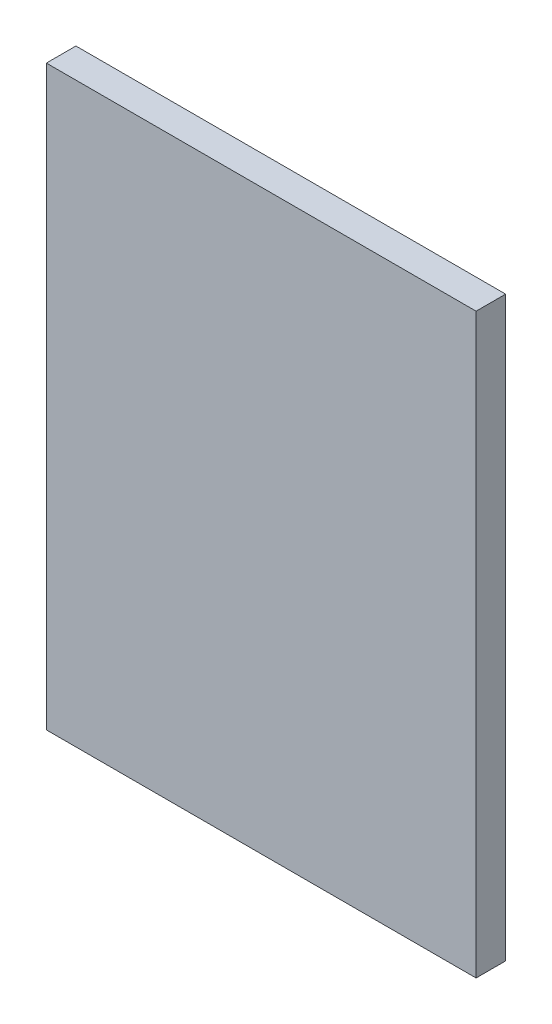
SolidWorks part; units mm, degrees
ref_plane "Front Plane" through (0, 0, 0) normal (0, 0, 1) x (1, 0, 0)
ref_plane "Top Plane" through (0, 0, 0) normal (0, 1, 0) x (1, 0, 0)
ref_plane "Right Plane" through (0, 0, 0) normal (1, 0, 0) x (0, 0, -1)
sketch "Sketch1" plane through (0, 0, 0) normal (0, 0, 1) x (1, 0, 0)
  line L1 (-17.45, -23.45) -> (17.45, -23.45)
  line L2 (-17.45, -23.45) -> (-17.45, 23.45)
  line L3 (-17.45, 23.45) -> (17.45, 23.45)
  line L4 (17.45, -23.45) -> (17.45, 23.45)
  line L5 (-17.45, -23.45) -> (17.45, 23.45) construction
  line L6 (-17.45, 23.45) -> (17.45, -23.45) construction
extrude "Envelope" add sketch "Sketch1" along normal blind 2.4
